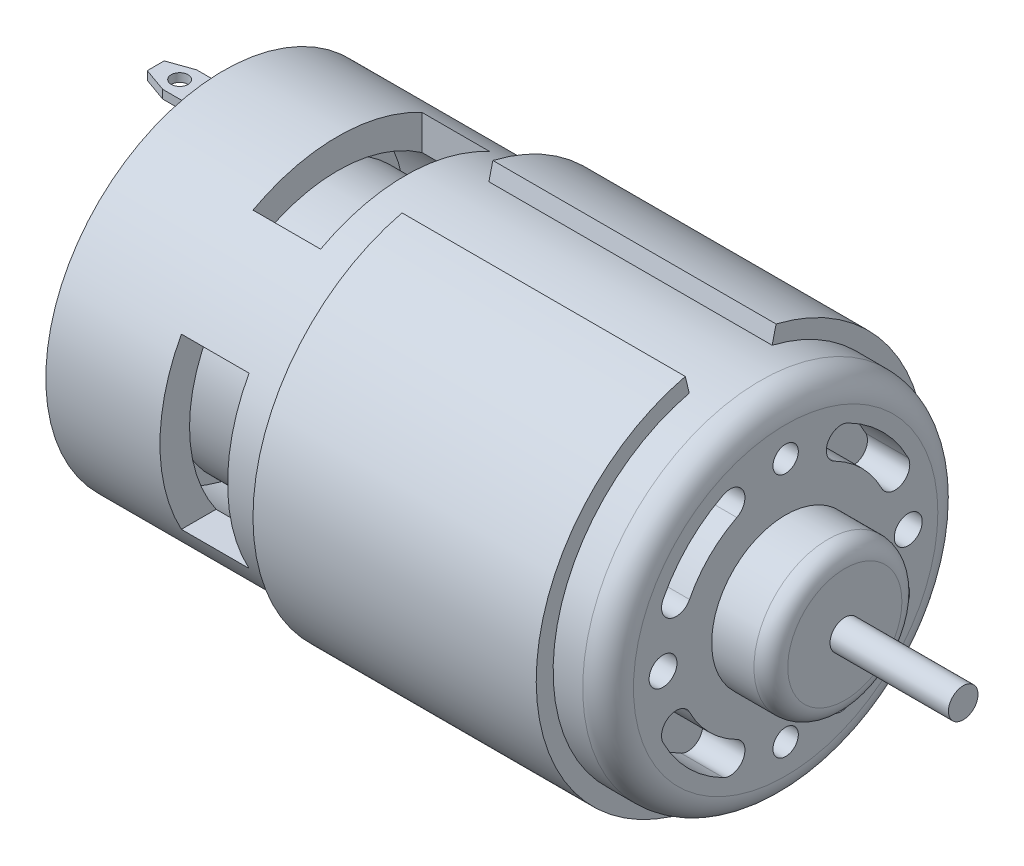
SolidWorks part; units mm, degrees
material "1060 Alloy"
ref_plane "Front Plane" through (0, 0, 0) normal (0, 0, 1) x (1, 0, 0)
ref_plane "Top Plane" through (0, 0, 0) normal (0, 1, 0) x (1, 0, 0)
ref_plane "Right Plane" through (0, 0, 0) normal (1, 0, 0) x (0, 0, -1)
sketch "Sketch1" plane through (0, 0, 0) normal (1, 0, 0) x (0, 0, -1)
  circle A0 centre (0, 0) radius 21
  dimension "D1" = 42
extrude "Boss-Extrude1" add sketch "Sketch1" along normal blind 66.5
fillet "Fillet1" radius 3 1 edges at (66.5, 0, -21)
sketch "Sketch2" plane through (66.5, 0, 0) normal (1, 0, 0) x (0, 0, -1)
  circle A0 centre (0, 0) radius 8.75
  dimension "D1" = 17.5
extrude "Boss-Extrude2" add sketch "Sketch2" along normal blind 7
fillet "Fillet2" radius 2 1 edges at (73.5, 0, -8.75)
sketch "Sketch3" plane through (73.5, 0, 0) normal (1, 0, 0) x (0, 0, -1)
  circle A0 centre (0, 0) radius 1.75
  dimension "D1" = 3.5
extrude "Boss-Extrude3" add sketch "Sketch3" along normal blind 14
ref_plane "Plane1" through (60, 0, 0) normal (1, 0, 0) x (0, 0, -1)
sketch "Sketch4" plane through (60, 0, 0) normal (1, 0, 0) x (0, 0, -1)
  line L0 (-5.3694, 22.3645) -> (-4.9025, 20.4197)
  line L1 (4.9025, 20.4197) -> (5.4896, 22.8652)
  circle A0 centre (0, 0) radius 23
  circle A1 centre (0, 0) radius 21 construction
  circle A2 centre (0, 0) radius 21
  dimension "D1" = 46
  dimension "D2" = 42
extrude "Boss-Extrude4" add sketch "Sketch4" against normal blind 33.5 contours A2 L0 A0 L1 region at (60, 21.2413, 5.7642)
sketch "Sketch5" plane through (0, 0, 0) normal (-1, 0, 0) x (0, 0, 1)
  line L0 (0, 21) -> (0, -21) construction
  line L2 (-2, 17.5) -> (2, 17.5)
  line L3 (-2, 17.5) -> (-2, 16.5)
  line L4 (-2, 16.5) -> (2, 16.5)
  line L5 (2, 17.5) -> (2, 16.5)
  line L6 (-2, 17.5) -> (2, 16.5) construction
  line L7 (-2, 16.5) -> (2, 17.5) construction
  line L8 (-2, -16.5) -> (2, -16.5)
  line L9 (-2, -16.5) -> (-2, -17.5)
  line L10 (-2, -17.5) -> (2, -17.5)
  line L11 (2, -16.5) -> (2, -17.5)
  line L12 (-2, -16.5) -> (2, -17.5) construction
  line L13 (-2, -17.5) -> (2, -16.5) construction
  circle A0 centre (0, 0) radius 21 construction
  arc A1 (-4.9025, 20.4197) -> (4.9025, 20.4197) centre (0, 0) ccw construction
  circle A2 centre (0, 0) radius 19
  point P7 (0, 17)
  point P12 (0, -17)
  dimension "D5" = 2
  dimension "D1" = 34
  dimension "D2" = 17
  dimension "D3" = 4
  dimension "D4" = 1
extrude "Cut-Extrude1" cut sketch "Sketch5" against normal blind 2
extrude "Boss-Extrude5" add sketch "Sketch5<3>" along normal blind 8 contours L4 L5 L2 L3 | L8 L11 L10 L9
sketch "Sketch5<3>" plane through (0, 0, 0) normal (-1, 0, 0) x (0, 0, 1) same geometry as "Sketch5"
sketch "Sketch6" plane through (0, -17.5, 0) normal (0, -1, 0) x (1, 0, 0)
  line L0 (-5.1716, -2) -> (-8, -1)
  line L1 (2, -2) -> (-8, -2) construction
  line L2 (-8, -2) -> (-8, 2) construction
  line L3 (-8, -1) -> (-8, 1)
  line L4 (-8, 1) -> (-5.1716, 2)
  line L5 (2, 2) -> (-8, 2) construction
  line L6 (-5.1716, -2) -> (-8, -2)
  line L7 (-8, -2) -> (-8, -1)
  line L8 (-7.7692, 1.1937) -> (-8, 1)
  line L9 (-8, 1) -> (-8, 2)
  line L10 (-8, 2) -> (-5.1716, 2)
  line M7 (2, 2) -> (-8, 2)
  line M8 (-8, 2) -> (-8, -2)
  line M9 (-8, -2) -> (2, -2)
  dimension "D1" = 3
  dimension "D2" = 1
extrude "Cut-Extrude2" cut sketch "Sketch6" against normal blind 37 contours L0 M9 M8 | L4 M8 M7 region at (-7.0572, -17.5, -1.6667) region at (-7.0572, -17.5, 1.6667)
ref_plane "Plane2" through (0, 21, 0) normal (0, 1, 0) x (1, 0, 0)
sketch "Sketch7" plane through (0, 21, 0) normal (0, 1, 0) x (1, 0, 0)
  line L0 (0, 0) -> (29.2331, 0) construction
  line L1 (21.5, -21) -> (21.5, 21) construction
  line L2 (0, -21) -> (26.5, -21) construction
  line L3 (26.5, 21) -> (0, 21) construction
  line L4 (26.5, 23) -> (26.5, -23) construction
  line L6 (21.5, -10) -> (13.5, -10)
  line L7 (21.5, -10) -> (21.5, 10)
  line L8 (21.5, 10) -> (13.5, 10)
  line L9 (13.5, -10) -> (13.5, 10)
  dimension "D1" = 5
  dimension "D2" = 10
  dimension "D3" = 10
  dimension "D4" = 8
extrude "Cut-Extrude3" cut sketch "Sketch7" against normal through all
pattern_circular "CirPattern1" count 2 every 90 about axis through (0, 0, 0) along (-1, 0, 0) of "Cut-Extrude3"
sketch "Sketch9" plane through (2, 0, 0) normal (-1, 0, 0) x (0, 0, 1)
  circle A0 centre (0, 0) radius 17.5
  dimension "D1" = 35
extrude "Boss-Extrude6" add sketch "Sketch9" against normal up to surface (64.5 mm away) up to face at (66.5, 0, -8.75)
sketch "Sketch10" plane through (0, 17.5, 0) normal (0, 1, 0) x (1, 0, 0)
  line L0 (-8, 0) -> (0, 0) construction
  line L1 (-8, 1) -> (-8, -1) construction
  line L2 (-5.1716, 2) -> (-5.1716, -2) construction
  line L3 (-8, 1) -> (-5.1716, 2) construction
  line L4 (2, 2) -> (-5.1716, 2) construction
  circle A0 centre (-5.1716, 0) radius 1
  dimension "D1" = 2
extrude "Cut-Extrude4" cut sketch "Sketch10" against normal through all and the other way through all
sketch "Sketch11" plane through (66.5, 0, 0) normal (1, 0, 0) x (0, 0, -1)
  line L0 (18, 0) -> (-18, 0) construction
  line L1 (0, 14.5) -> (0, -14.5) construction
  line L2 (-6.5648, 12.9288) -> (0, 14.5)
  line L3 (-12.9288, 6.5648) -> (-14.5, 0)
  circle A0 centre (0, 0) radius 14.5
  circle A1 centre (0, 0) radius 18 construction
  circle A2 centre (0, -14.5) radius 1.5
  circle A3 centre (0, 14.5) radius 1.5
  arc A4 (-12.9288, 6.5648) -> (-6.5648, 12.9288) centre (0, 0) cw construction
  arc A5 (-7.3571, 14.4891) -> (-14.4891, 7.3571) centre (0, 0) ccw
  arc A6 (-5.7725, 11.3684) -> (-11.3684, 5.7725) centre (0, 0) ccw
  arc A7 (-5.7725, 11.3684) -> (-7.3571, 14.4891) centre (-6.5648, 12.9288) ccw
  arc A8 (-14.4891, 7.3571) -> (-11.3684, 5.7725) centre (-12.9288, 6.5648) ccw
  arc A9 (6.5648, 12.9288) -> (12.9288, 6.5648) centre (0, 0) cw construction
  arc A10 (14.4891, 7.3571) -> (7.3571, 14.4891) centre (0, 0) ccw
  arc A11 (11.3684, 5.7725) -> (5.7725, 11.3684) centre (0, 0) ccw
  arc A12 (11.3684, 5.7725) -> (14.4891, 7.3571) centre (12.9288, 6.5648) ccw
  arc A13 (7.3571, 14.4891) -> (5.7725, 11.3684) centre (6.5648, 12.9288) ccw
  arc A14 (12.9288, -6.5648) -> (6.5648, -12.9288) centre (0, 0) cw construction
  arc A15 (7.3571, -14.4891) -> (14.4891, -7.3571) centre (0, 0) ccw
  arc A16 (5.7725, -11.3684) -> (11.3684, -5.7725) centre (0, 0) ccw
  arc A17 (5.7725, -11.3684) -> (7.3571, -14.4891) centre (6.5648, -12.9288) ccw
  arc A18 (14.4891, -7.3571) -> (11.3684, -5.7725) centre (12.9288, -6.5648) ccw
  arc A19 (-6.5648, -12.9288) -> (-12.9288, -6.5648) centre (0, 0) cw construction
  arc A20 (-14.4891, -7.3571) -> (-7.3571, -14.4891) centre (0, 0) ccw
  arc A21 (-11.3684, -5.7725) -> (-5.7725, -11.3684) centre (0, 0) ccw
  arc A22 (-11.3684, -5.7725) -> (-14.4891, -7.3571) centre (-12.9288, -6.5648) ccw
  arc A23 (-7.3571, -14.4891) -> (-5.7725, -11.3684) centre (-6.5648, -12.9288) ccw
  point P15 (-10.253, 10.253)
  point P28 (10.253, 10.253)
  point P35 (10.253, -10.253)
  point P42 (-10.253, -10.253)
  dimension "D1" = 29
  dimension "D2" = 3
  dimension "D3" = 3
  dimension "D4" = 3.5
  dimension "D5" = 9
  dimension "D6" = 4
hole_wizard "M4 Tapped Hole1" positions "3DSketch1" profile "Sketch12" tap size "M4" standard "KS"
sketch3d "3DSketch1"
  line L0 (66.5, 0, -18) -> (66.5, 0, 18) construction
  circle A0 centre (66.5, 0, 0) radius 14.5 construction
  point P0 (66.5, 0, 14.5)
  point P4 (81, 0, 0)
  point P7 (66.5, 0, -14.5)
cosmetic thread "Hole Thread1" parameters "D1"=8, "D2"=4
cosmetic thread "Hole Thread2" parameters "D1"=8, "D2"=4
sketch "Sketch12" plane through (66.5, 0, 14.5) normal (0, 1, 0) x (0, 0, -1)
  line L0 (0, 0) -> (0, 11.0914)
  line L1 (0, 11.0914) -> (1.65, 10.1)
  line L2 (1.65, 10.1) -> (1.65, 0)
  line L5 (1.65, 0) -> (0, 0)
  line L10 (0, 11.0914) -> (-1.65, 10.1) construction
  line L11 (0, -6.35) -> (0, 107.95) construction
  dimension "Tap Drill Dia." = 3.3
  dimension "Tap Drill Depth" = 10.1
  dimension "Drill Angle" = 118
extrude "Cut-Extrude6" cut sketch "Sketch11" against normal blind 5 contours L3 A8 A6 A7 L2 A0 | A20 A23 A0 A22 | A0 A23 A21 A22 | A0 A2 | A0 A2 | A0 A18 A16 A17 | A15 A18 A0 A17 | A0 A13 A11 A12 | A10 A13 A0 A12 | L2 A3 A0 | A0 A3 L2 | A0 A3 | L2 A7 A0 | A0 A8 L3 | A6 A8 A5 A7 region at (66.5, 13.2966, 5.4913) region at (66.5, 9.3901, 9.3901) region at (66.5, 5.4913, 13.2966) region at (66.5, 14.367, 0.9678) region at (66.5, 13.8135, -0.0675) region at (66.5, 15.1224, 0) region at (66.5, 10.5604, -10.5604) region at (66.5, 9.3902, -9.3902) region at (66.5, -9.3902, 9.3902) region at (66.5, -10.5604, 10.5604) region at (66.5, -13.8496, 0) region at (66.5, -15.1224, 0) region at (66.5, -10.5604, -10.5604) region at (66.5, -9.3902, -9.3902)
sketch "Sketch13" plane through (2, 0, 0) normal (-1, 0, 0) x (0, 0, 1)
  circle A0 centre (0, 0) radius 15
  dimension "D1" = 30
extrude "Boss-Extrude7" add sketch "Sketch13" along normal blind 1
chamfer "Chamfer1" distance 2 distance2 3.5 1 edges at (1, 0, 15) first distance on face at (1, 0, 15)
sketch "Sketch15" plane through (2, 0, 0) normal (-1, 0, 0) x (0, 0, 1)
  line L0 (1, 17) -> (-1, 17) construction
  line L1 (1, 17.5) -> (1, 16.5) construction
  line L2 (-1, 17.5) -> (-1, 16.5) construction
  line L3 (0, 17.5) -> (0, 16.5315) construction
  line L4 (19, 0) -> (-19, 0) construction
  line L5 (3, 19.5) -> (-3, 19.5)
  line L6 (3, 19.5) -> (3, 14.5)
  line L7 (3, 14.5) -> (-3, 14.5)
  line L8 (-3, 19.5) -> (-3, 14.5)
  line L9 (3, 19.5) -> (-3, 14.5) construction
  line L10 (3, 14.5) -> (-3, 19.5) construction
  line L11 (-3, -19.5) -> (-3, -14.5)
  line L12 (3, -19.5) -> (-3, -19.5)
  line L13 (3, -19.5) -> (3, -14.5)
  line L14 (3, -14.5) -> (-3, -14.5)
  circle A0 centre (0, 0) radius 19 construction
  circle A1 centre (0, 0) radius 19 construction
  point P10 (0, 17)
  dimension "D1" = 6
  dimension "D2" = 5
extrude "Boss-Extrude8" add sketch "Sketch15" along normal blind 1
sketch "Sketch16" plane through (2, 0, 0) normal (-1, 0, 0) x (0, 0, 1)
  line L0 (-19, 0) -> (19, 0) construction
  arc A0 (-3, 18.7617) -> (-3, -18.7617) centre (0, 0) ccw construction
chamfer "Chamfer2" distance 1 angle 32 6 edges at (1, -16.6308, -3) (1, -14.5, 0) (1, -16.6308, 3) (1, 16.6308, 3) (1, 16.6308, -3) (1, 14.5, 0) first distance on face at (1, -17, 0) first distance on face at (1, 17, 0)
sketch "Sketch17" plane through (1, 0, 0) normal (-1, 0, 0) x (0, 0, 1)
  line L0 (-19, 0) -> (19, 0) construction
  circle A0 centre (0, 0) radius 6.1849
extrude "Boss-Extrude9" add sketch "Sketch17" along normal blind 3
fillet "Fillet3" radius 1 1 edges at (-2, 0, 6.1849)
sketch "Sketch19" plane through (-2, 0, 0) normal (-1, 0, 0) x (0, 0, 1)
  circle A0 centre (0, 0) radius 2
  dimension "D1" = 4
extrude "Boss-Extrude10" add sketch "Sketch19" along normal blind 3
fillet "Fillet4" radius 1 1 edges at (-5, 0, 2)
sketch "Sketch20" plane through (1, 0, 0) normal (-1, 0, 0) x (0, 0, 1)
  line L0 (-9, 0) -> (9, 0) construction
  line L1 (0, 0) -> (6.364, -6.364) construction
  line L2 (0, 11.5) -> (0, -11.5) construction
  line L3 (0, 0) -> (-6.364, 6.364) construction
  circle A0 centre (0, 0) radius 9
  circle A1 centre (0, 0) radius 11.5 construction
  arc A2 (4.1002, 8.0118) -> (8.0118, 4.1002) centre (0, 0) cw construction
  arc A3 (-8.0118, 4.1002) -> (-4.1002, 8.0118) centre (0, 0) cw construction
  arc A4 (-4.6696, 9.1245) -> (-9.1245, 4.6696) centre (0, 0) ccw
  arc A5 (-3.5307, 6.899) -> (-6.899, 3.5307) centre (0, 0) ccw
  arc A6 (-3.5307, 6.899) -> (-4.6696, 9.1245) centre (-4.1002, 8.0118) ccw
  arc A7 (-9.1245, 4.6696) -> (-6.899, 3.5307) centre (-8.0118, 4.1002) ccw
  arc A8 (9.1245, 4.6696) -> (4.6696, 9.1245) centre (0, 0) ccw
  arc A9 (6.899, 3.5307) -> (3.5307, 6.899) centre (0, 0) ccw
  arc A10 (6.899, 3.5307) -> (9.1245, 4.6696) centre (8.0118, 4.1002) ccw
  arc A11 (4.6696, 9.1245) -> (3.5307, 6.899) centre (4.1002, 8.0118) ccw
  arc A12 (8.0118, -4.1002) -> (4.1002, -8.0118) centre (0, 0) cw construction
  arc A13 (4.6696, -9.1245) -> (9.1245, -4.6696) centre (0, 0) ccw
  arc A14 (3.5307, -6.899) -> (6.899, -3.5307) centre (0, 0) ccw
  arc A15 (3.5307, -6.899) -> (4.6696, -9.1245) centre (4.1002, -8.0118) ccw
  arc A16 (9.1245, -4.6696) -> (6.899, -3.5307) centre (8.0118, -4.1002) ccw
  arc A17 (-4.1002, -8.0118) -> (-8.0118, -4.1002) centre (0, 0) cw construction
  arc A18 (-9.1245, -4.6696) -> (-4.6696, -9.1245) centre (0, 0) ccw
  arc A19 (-6.899, -3.5307) -> (-3.5307, -6.899) centre (0, 0) ccw
  arc A20 (-6.899, -3.5307) -> (-9.1245, -4.6696) centre (-8.0118, -4.1002) ccw
  arc A21 (-4.6696, -9.1245) -> (-3.5307, -6.899) centre (-4.1002, -8.0118) ccw
  point P8 (-6.364, 6.364)
  point P24 (6.364, 6.364)
  point P32 (6.364, -6.364)
  point P39 (-6.364, -6.364)
  dimension "D1" = 2.5
  dimension "D2" = 2.5
  dimension "D3" = 2.8
  dimension "D4" = 45
  dimension "D5" = 4
extrude "Cut-Extrude7" cut sketch "Sketch20" against normal blind 5 contours A0 A21 A19 A20 | A18 A21 A0 A20 | A0 A7 A5 A6 | A4 A7 A0 A6 | A0 A11 A9 A10 | A8 A11 A0 A10 | A0 A16 A14 A15 | A13 A16 A0 A15 region at (1, 5.7673, 5.7673) region at (1, 6.5993, 6.5993) region at (1, -6.5993, 6.5993) region at (1, -5.7673, 5.7673) region at (1, 5.7673, -5.7673) region at (1, 6.5993, -6.5993) region at (1, -6.5993, -6.5993) region at (1, -5.7673, -5.7673)
ref_plane "Plane4" through (30, 0, 0) normal (1, 0, 0) x (0, 0, -1)
sketch "Sketch22" plane through (30, 0, 0) normal (1, 0, 0) x (0, 0, -1)
  circle A0 centre (0, 0) radius 15
  circle A1 centre (0, 0) radius 17.5
  dimension "D1" = 35
  dimension "D2" = 30
extrude "Cut-Extrude8" cut sketch "Sketch22" against normal blind 26
ref_plane "Plane5" through (4, 0, 0) normal (1, 0, 0) x (0, 0, -1)
sketch "Sketch23" plane through (4, 0, 0) normal (1, 0, 0) x (0, 0, -1)
  circle A0 centre (0, 0) radius 17.5
  circle A1 centre (0, 0) radius 6
  dimension "D1" = 35
  dimension "D2" = 12
extrude "Cut-Extrude9" cut sketch "Sketch23" along normal blind 5
